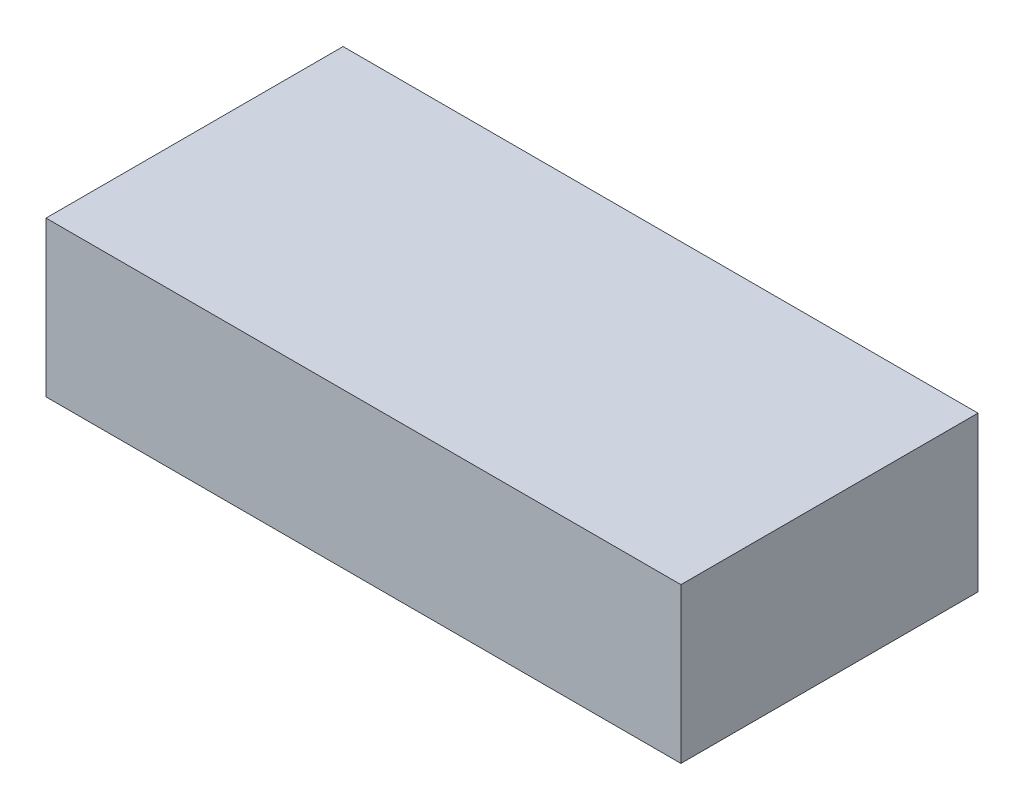
SolidWorks part; units mm, degrees
ref_plane "Front Plane" through (0, 0, 0) normal (0, 0, 1) x (1, 0, 0)
ref_plane "Top Plane" through (0, 0, 0) normal (0, 1, 0) x (1, 0, 0)
ref_plane "Right Plane" through (0, 0, 0) normal (1, 0, 0) x (0, 0, -1)
sketch "Sketch1" plane through (0, 0, 0) normal (0, 1, 0) x (1, 0, 0)
  line L1 (44.69, -20.91) -> (-44.69, -20.91)
  line L2 (44.69, -20.91) -> (44.69, 20.91)
  line L3 (44.69, 20.91) -> (-44.69, 20.91)
  line L4 (-44.69, -20.91) -> (-44.69, 20.91)
  line L5 (44.69, -20.91) -> (-44.69, 20.91) construction
  line L6 (44.69, 20.91) -> (-44.69, -20.91) construction
  circle A0 centre (-25.39, 11.93) radius 2.2
  circle A1 centre (-25.39, -12.11) radius 2.2
  circle A2 centre (14.65, 11.93) radius 2.2
  circle A3 centre (14.65, -12.11) radius 2.2
  point P0 (0, 0)
  point P12 (-63.9645, 30.3951)
  point P15 (0, 0)
  dimension "D4" = 4.4
  dimension "D1" = 41.82
  dimension "D2" = 89.38
  dimension "D3" = 8.98
  dimension "D5" = 19.3
  dimension "D7" = 19.3
  dimension "D8" = 8.98
  dimension "D9" = 24.04
  dimension "D6" = 24.04
  dimension "D10" = 30.04
extrude "Boss-Extrude6" add sketch "Sketch1" along normal blind 21.8 contours L2 L1 L4 L3
extrude "Cut-Extrude2" cut sketch "Sketch1<13>" along normal blind 10 contours A0 | A2 | A3 | A1
sketch "Sketch1<13>" plane through (0, 0, 0) normal (0, 1, 0) x (1, 0, 0) same geometry as "Sketch1"
equation "\"D3@Sketch1\"=6.78+\"D4@Sketch1\"/2"
equation "\"D5@Sketch1\"=17.1+\"D4@Sketch1\"/2"
equation "\"D7@Sketch1\"=\"D5@Sketch1\""
equation "\"D8@Sketch1\"=\"D3@Sketch1\""
equation "\"D6@Sketch1\"=19.64+\"D4@Sketch1\""
equation "\"D9@Sketch1\"=\"D6@Sketch1\""
equation "\"D10@Sketch1\"=27.84+\"D4@Sketch1\"/2"
